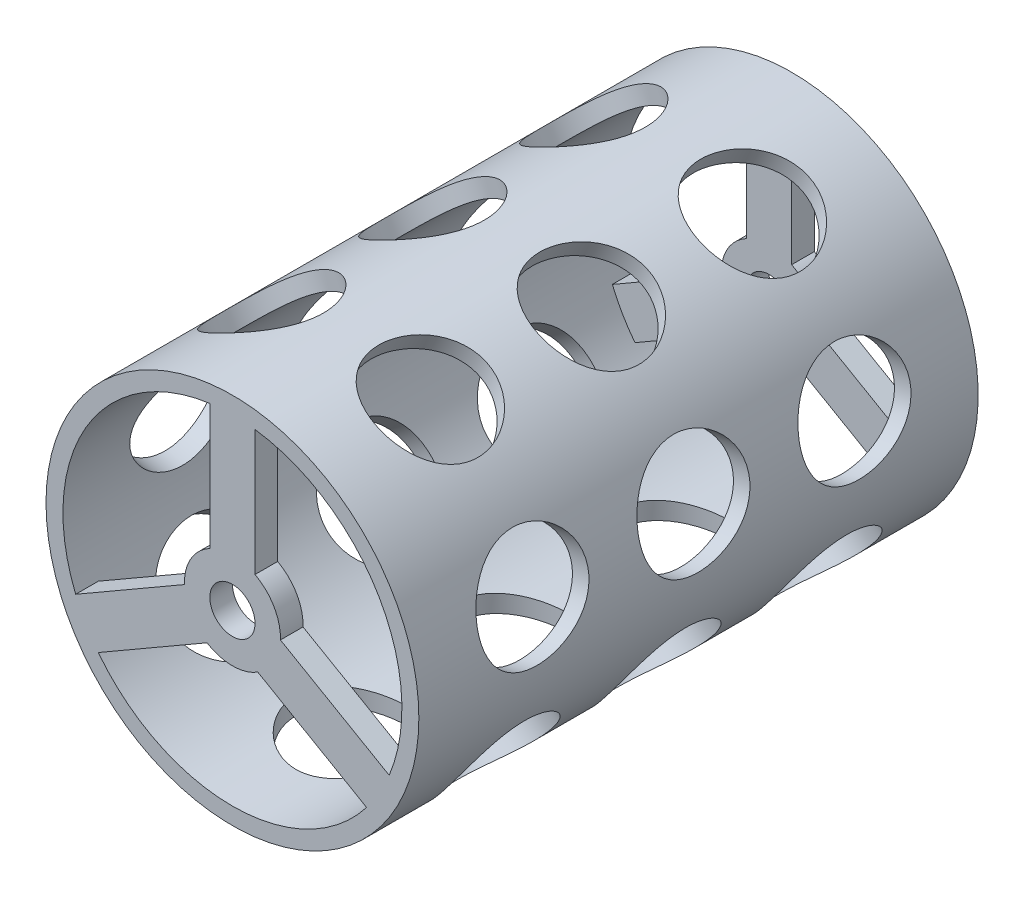
SolidWorks part; units mm, degrees
ref_plane "Ön Düzlem" through (0, 0, 0) normal (0, 0, 1) x (1, 0, 0)
ref_plane "Üst Düzlem" through (0, 0, 0) normal (0, 1, 0) x (1, 0, 0)
ref_plane "Sağ Düzlem" through (0, 0, 0) normal (1, 0, 0) x (0, 0, -1)
sketch "Çizim1" plane through (0, 0, 0) normal (0, 0, 1) x (1, 0, 0)
  circle A0 centre (0, 0) radius 30
  circle A1 centre (0, 0) radius 33
extrude "Yükseklik-Ekstrüzyon1" add sketch "Çizim1" along normal blind 95
sketch "Çizim2" plane through (0, 0, 0) normal (0, 0, -1) x (-1, 0, 0)
  circle A0 centre (0, 0) radius 33
extrude "Yükseklik-Ekstrüzyon2" add sketch "Çizim2" along normal blind 4
sketch "Çizim3" plane through (0, 0, 95) normal (0, 0, 1) x (1, 0, 0)
  circle A0 centre (0, 0) radius 33
extrude "Yükseklik-Ekstrüzyon3" add sketch "Çizim3" along normal blind 4 from offset 4 offset against normal yes
sketch "Çizim4" plane through (0, 0, -4) normal (0, 0, -1) x (-1, 0, 0)
  line L0 (8.4952, -0.2859) -> (27.7488, -11.402)
  line L1 (-4, 7.5) -> (-4, 29.7321)
  line L2 (4, 29.7321) -> (4, 7.5)
  line L3 (23.7488, -18.3302) -> (4.4952, -7.2141)
  line L4 (-4.4952, -7.2141) -> (-23.7488, -18.3302)
  line L5 (-27.7488, -11.402) -> (-8.4952, -0.2859)
  circle A0 centre (0, 0) radius 33
  arc A1 (-23.7488, -18.3302) -> (23.7488, -18.3302) centre (0, 0) ccw
  arc A2 (-4.4952, -7.2141) -> (4.4952, -7.2141) centre (0, 0) ccw
  arc A3 (-4, 7.5) -> (-8.4952, -0.2859) centre (0, 0) ccw
  arc A4 (8.4952, -0.2859) -> (4, 7.5) centre (0, 0) ccw
  arc A5 (27.7488, -11.402) -> (-27.7488, -11.402) centre (0, 0) ccw
  point P19 (0, 0)
  dimension "D1" = 3
extrude "Kes-Ekstrüzyon1" cut sketch "Çizim4" against normal blind 122 contours L1 A5 L5 A3 | L0 A5 L2 A4 | A2 L4 A1 L3 region at (-16.5918, 9.5793, -4) region at (16.5918, 9.5793, -4) region at (0, -19.1586, -4)
sketch "Çizim5" plane through (0, 0, -4) normal (0, 0, -1) x (-1, 0, 0)
  circle A0 centre (0, 0) radius 4
extrude "Kes-Ekstrüzyon2" cut sketch "Çizim5" against normal blind 122
sketch "Çizim6" plane through (0, 0, 0) normal (0, 1, 0) x (1, 0, 0)
  line L0 (33, 4) -> (-33, 4) construction
  line L1 (-33, -95) -> (33, -95) construction
  circle A0 centre (0, -17) radius 9.75
  circle A1 centre (0, -45.5) radius 9.75
  circle A2 centre (0, -74) radius 9.75
  dimension "D1" = 21
  dimension "D2" = 28.5
  dimension "D4" = 19.5
  dimension "D5" = 19.5
  dimension "D6" = 19.5
  dimension "D7" = 21
extrude "Kes-Ekstrüzyon3" cut sketch "Çizim6" against normal blind 75 and the other way blind 6
pattern_circular "Dairesel Kaplama1" count 7 over 360 about axis through (0, 0, -4) along (0, 0, -1) of "Kes-Ekstrüzyon3"
